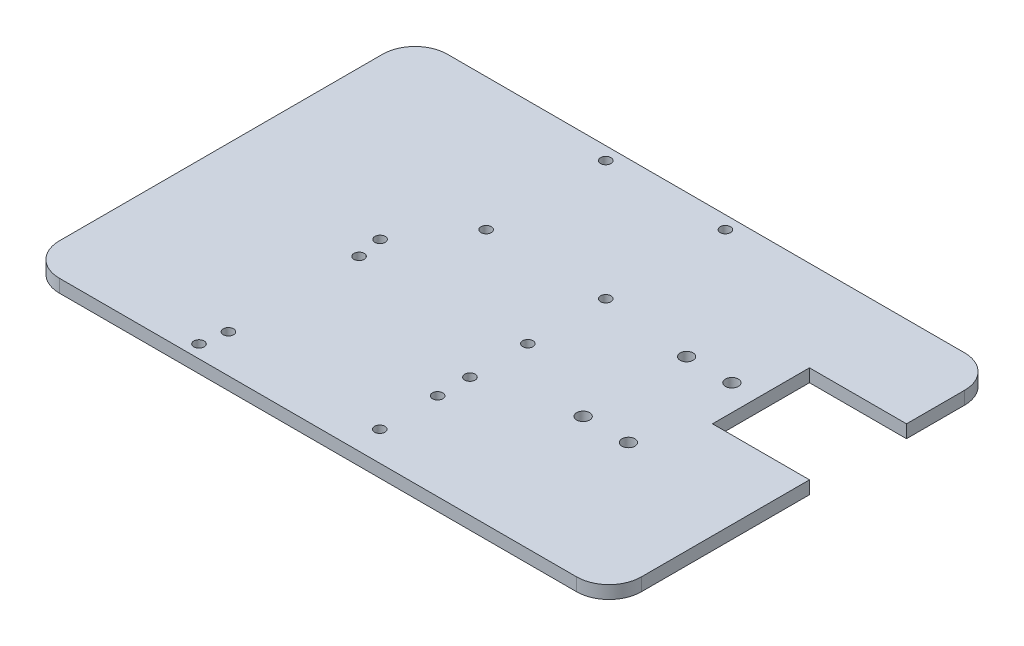
SolidWorks part; units mm, degrees
ref_plane "前视基准面" through (0, 0, 0) normal (0, 0, 1) x (1, 0, 0)
ref_plane "上视基准面" through (0, 0, 0) normal (0, 1, 0) x (1, 0, 0)
ref_plane "右视基准面" through (0, 0, 0) normal (1, 0, 0) x (0, 0, -1)
other "Configuration Table"
sketch "草图1" plane through (0, 0, 0) normal (0, 1, 0) x (1, 0, 0)
  line L1 (-90, -60) -> (90, -60)
  line L2 (-90, -60) -> (-90, 60)
  line L3 (-90, 60) -> (90, 60)
  line L4 (90, -60) -> (90, 60)
  line L5 (-90, -60) -> (90, 60) construction
  line L6 (-90, 60) -> (90, -60) construction
  point P0 (0, 0)
  dimension "D1" = 120
  dimension "D2" = 180
extrude "凸台-拉伸1" add sketch "草图1" along normal blind 4
sketch "草图2" plane through (0, 4, 0) normal (0, 1, 0) x (1, 0, 0)
  line L0 (90, -60) -> (90, 60) construction
  line L1 (66, -25) -> (85, -25) construction
  line L2 (66, -25) -> (66, 25) construction
  line L3 (66, 25) -> (85, 25) construction
  line L4 (85, -25) -> (85, 25) construction
  line L5 (66, -25) -> (85, 25) construction
  line L6 (66, 25) -> (85, -25) construction
  circle A0 centre (66, 25) radius 1.6
  circle A1 centre (66, -25) radius 1.6
  circle A2 centre (85, -25) radius 1.6
  circle A3 centre (85, 25) radius 1.6
  circle A7 centre (80.7, 7) radius 3
  point P0 (75.5, 0)
  dimension "D4" = 3.2
  dimension "D5" = 4.3
  dimension "D7" = 6
  dimension "D1" = 19
  dimension "D2" = 50
  dimension "D3" = 5
  dimension "D6" = 18
sketch "草图3" plane through (0, 4, 0) normal (0, 1, 0) x (1, 0, 0)
  line L0 (90, -60) -> (90, 60) construction
  line L1 (60, 2) -> (100, 2)
  line L2 (60, 2) -> (60, 32)
  line L3 (60, 32) -> (100, 32)
  line L4 (100, 2) -> (100, 32)
  line L5 (60, 2) -> (100, 32) construction
  line L6 (60, 32) -> (100, 2) construction
  line L7 (90, 60) -> (-90, 60) construction
  point P0 (80, 17)
  dimension "D1" = 40
  dimension "D2" = 30
  dimension "D3" = 10
  dimension "D4" = 28
extrude "切除-拉伸2" cut sketch "草图3" against normal blind 4
sketch "草图4" plane through (0, 4, 0) normal (0, 1, 0) x (1, 0, 0)
  line L0 (90, 60) -> (-90, 60) construction
  line L1 (-27, 56) -> (10, 56) construction
  line L2 (-27, 56) -> (-27, 19) construction
  line L3 (-27, 19) -> (10, 19) construction
  line L4 (10, 56) -> (10, 19) construction
  line L6 (60, 32) -> (60, 2) construction
  circle A0 centre (-27, 56) radius 1.6
  circle A1 centre (10, 56) radius 1.6
  circle A2 centre (10, 19) radius 1.6
  circle A3 centre (-27, 19) radius 1.6
  dimension "D4" = 3.2
  dimension "D1" = 37
  dimension "D2" = 4
  dimension "D3" = 50
extrude "切除-拉伸3" cut sketch "草图4" against normal blind 4
sketch "草图5" plane through (0, 4, 0) normal (0, 1, 0) x (1, 0, 0)
  line L0 (-90, -60) -> (90, -60) construction
  line L1 (-40.8, -56) -> (10, -56) construction
  line L2 (-40.8, -56) -> (-40.8, -7.8) construction
  line L3 (-40.8, -7.8) -> (10, -7.8) construction
  line L4 (10, -56) -> (10, -7.8) construction
  line L5 (-18.0867, -28) -> (49981.9133, -28) construction
  line L8 (60, 32) -> (60, 2) construction
  circle A0 centre (-39.5, -7.8) radius 1.6
  circle A1 centre (10, -23) radius 1.6
  circle A2 centre (10, -50.9) radius 1.6
  circle A3 centre (-40.8, -56) radius 1.6
  circle A4 centre (10, -5.1) radius 1.6
  circle A5 centre (10, -33) radius 1.6
  circle A6 centre (-40.8, 0) radius 1.6
  circle A7 centre (-39.5, -48.2) radius 1.6
  dimension "D8" = 3.2
  dimension "D1" = 48.2
  dimension "D2" = 50.8
  dimension "D3" = 4
  dimension "D4" = 50
  dimension "D5" = 1.3
  dimension "D6" = 15.2
  dimension "D7" = 27.9
  dimension "D9" = 32
extrude "切除-拉伸4" cut sketch "草图5" against normal blind 4
sketch "草图7" plane through (0, 0, 0) normal (0, -1, 0) x (1, 0, 0)
  line L0 (0, 0) -> (130.1672, 0) construction
  line L1 (60, -32) -> (60, -2) construction
  circle A0 centre (52, 16) radius 2
  circle A1 centre (38, 16) radius 2
  circle A2 centre (52, -16) radius 2
  circle A3 centre (38, -16) radius 2
  dimension "D2" = 4
  dimension "D5" = 4
  dimension "D1" = 8
  dimension "D3" = 16
  dimension "D4" = 0
  dimension "D6" = 14
  dimension "D7" = 16
extrude "切除-拉伸5" cut sketch "草图7" against normal blind 10
fillet "圆角1" radius 10 4 edges at (90, 2, 60) (90, 2, -60) (-90, 2, -60) (-90, 2, 60)
